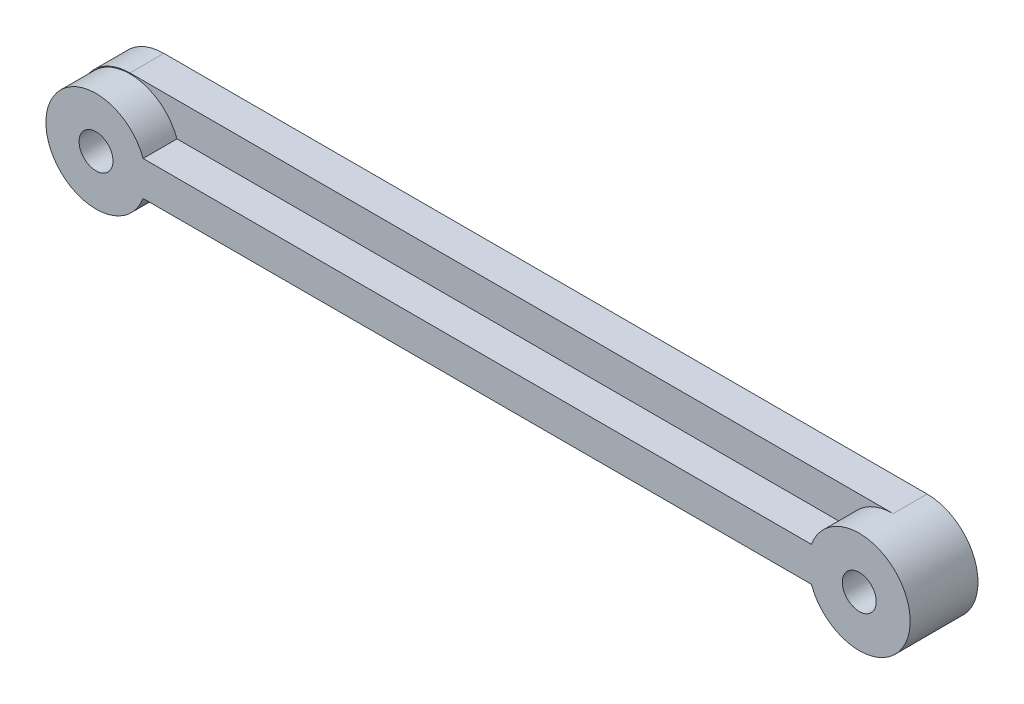
SolidWorks part; units mm, degrees
ref_plane "前视基准面" through (0, 0, 0) normal (0, 0, 1) x (1, 0, 0)
ref_plane "上视基准面" through (0, 0, 0) normal (0, 1, 0) x (1, 0, 0)
ref_plane "右视基准面" through (0, 0, 0) normal (1, 0, 0) x (0, 0, -1)
other "Configuration Table"
sketch "草图1" plane through (0, 0, 0) normal (0, 0, 1) x (1, 0, 0)
  line L0 (-1000, 0) -> (0, 0) construction
  line L2 (0, 1.5) -> (22.5, 1.5)
  line L3 (0, -1.5) -> (22.5, -1.5)
  line L4 (24, 0) -> (49000, 0) construction
  arc A0 (0, 1.5) -> (0, -1.5) centre (0, 0) ccw
  arc A1 (22.5, -1.5) -> (22.5, 1.5) centre (22.5, 0) ccw
  circle A2 centre (0, 0) radius 0.5
  circle A3 centre (22.5, 0) radius 0.5
  dimension "D1" = 3
  dimension "D3" = 1.5
  dimension "D4" = 1
  dimension "D5" = 1
  dimension "D2" = 22.5
extrude "凸台-拉伸1" add sketch "草图1" along normal blind 1
sketch "草图2" plane through (0, 0, 1) normal (0, 0, 1) x (1, 0, 0)
  line L0 (1.3868, 0.5099) -> (21.0893, 0.5099)
  line L1 (21.0893, -0.5099) -> (1.3868, -0.5099)
  arc A0 (1.3868, 0.5099) -> (1.3868, -0.5099) centre (0, 0) ccw
  arc A2 (21.0893, -0.5099) -> (21.0893, 0.5099) centre (22.5, 0) ccw
  circle A4 centre (0, 0) radius 0.5
  circle A5 centre (22.5, 0) radius 0.5
  point P8 (21.1167, 0.5)
extrude "凸台-拉伸3" add sketch "草图2" along normal blind 1
